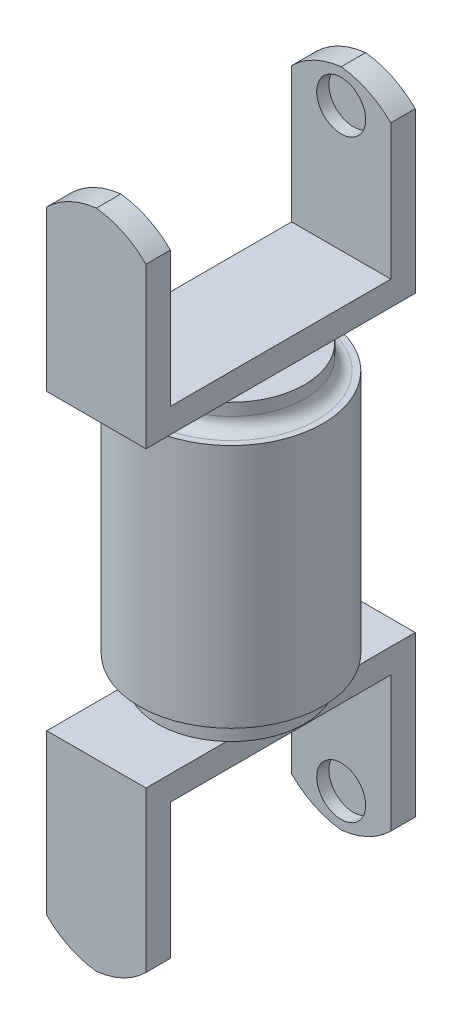
SolidWorks part; units mm, degrees
ref_plane "Front Plane" through (0, 0, 0) normal (0, 0, 1) x (1, 0, 0)
ref_plane "Top Plane" through (0, 0, 0) normal (0, 1, 0) x (1, 0, 0)
ref_plane "Right Plane" through (0, 0, 0) normal (1, 0, 0) x (0, 0, -1)
sketch "Sketch1" plane through (0, 0, 0) normal (0, 1, 0) x (1, 0, 0)
  circle A0 centre (0, 0) radius 7.5
  dimension "D1" = 15
extrude "Boss-Extrude1" add sketch "Sketch1" along normal blind 10
sketch "Sketch5" plane through (0, 10, 0) normal (0, 1, 0) x (1, 0, 0)
  circle A0 centre (0, 0) radius 6
  dimension "D1" = 12
extrude "Boss-Extrude2" add sketch "Sketch5" along normal blind 2
fillet "Fillet2" radius 1 1 edges at (0, 10, 6)
sketch "Sketch6" plane through (0, 0, 0) normal (1, 0, 0) x (0, 0, -1)
  line L0 (6, 12) -> (-6, 12) construction
  line L1 (6, 12) -> (-6, 12)
  line L2 (6, 12) -> (11, 12)
  line L3 (11, 12) -> (11, 27)
  line L4 (11, 27) -> (9, 27)
  line L5 (9, 27) -> (9, 14)
  line L6 (9, 14) -> (-9, 14)
  line L7 (-9, 14) -> (-9, 27)
  line L8 (-9, 27) -> (-11, 27)
  line L9 (-11, 27) -> (-11, 12)
  line L10 (-11, 12) -> (-6, 12)
  dimension "D1" = 15
  dimension "D2" = 2
  dimension "D3" = 13
  dimension "D4" = 5
extrude "Boss-Extrude3" add sketch "Sketch6" along normal blind 6 and the other way blind 6
sketch "Sketch9" plane through (0, 0, 11) normal (0, 0, 1) x (1, 0, 0)
  line L0 (0, 27) -> (0, 12) construction
  line L4 (-6, 12) -> (6, 12)
  line L5 (6, 12) -> (6, 27)
  line L6 (6, 27) -> (-6, 27)
  line L7 (-6, 27) -> (-6, 12)
  line L8 (-6, 12) -> (6, 12)
  line L9 (6, 12) -> (6, 27)
  line L10 (6, 27) -> (-6, 27)
  line L11 (-6, 27) -> (-6, 12)
  arc A0 (0, 27) -> (-6, 19.5) centre (0.75, 20.25) ccw
  arc A1 (0, 27) -> (6, 19.5) centre (-0.75, 20.25) cw
  line M7 (6, 12) -> (6, 27)
  line M8 (6, 27) -> (-6, 27)
  line M9 (-6, 27) -> (-6, 12)
  dimension "D1" = 0
extrude "Cut-Extrude4" cut sketch "Sketch9" against normal blind 29 contours A0 L10 M9 | A1 M8 M7 region at (-4.5286, 25.5286, 11) region at (4.5286, 25.5286, 11)
sketch "Sketch10" plane through (0, 0, 9) normal (0, 0, -1) x (-1, 0, 0)
  line L0 (6, 14) -> (6, 21) construction
  circle A0 centre (0, 24.25) radius 2
  arc A1 (6, 21) -> (0, 27) centre (-0.75, 20.25) ccw construction
  dimension "D1" = 4
  dimension "D2" = 4
  dimension "D3" = 6
extrude "Cut-Extrude5" cut sketch "Sketch10" against normal blind 1 and the other way blind 19
mirror "Mirror2" about plane through (0, 0, 0) normal (0, 1, 0) of "Boss-Extrude1"
mirror "Mirror9" about plane through (0, 0, 0) normal (0, 1, 0) of "Boss-Extrude3", "Boss-Extrude2"
mirror "Mirror11" about plane through (0, 0, 0) normal (0, 1, 0) of "Cut-Extrude5", "Cut-Extrude4"
sketch "Sketch11" plane through (0, 0, -11) normal (0, 0, -1) x (-1, 0, 0)
  line L0 (-4.0523, 25.0523) -> (-4.0523, 12)
  line L1 (4.0523, 25.0523) -> (4.0523, 12)
  line L3 (-6, 21) -> (-6, 12)
  line L4 (-6, 12) -> (6, 12)
  line L5 (6, 12) -> (6, 21)
  line L6 (-6, 21) -> (-6, 12)
  line L7 (-6, 12) -> (6, 12)
  line L8 (6, 12) -> (6, 21)
  arc A2 (0, 27) -> (-6, 21) centre (0.75, 20.25) ccw
  arc A3 (6, 21) -> (0, 27) centre (-0.75, 20.25) ccw
  arc A4 (0, 27) -> (-6, 21) centre (0.75, 20.25) ccw
  arc A5 (6, 21) -> (0, 27) centre (-0.75, 20.25) ccw
  arc M6 (0, 27) -> (-6, 21) centre (0.75, 20.25) ccw
  line M7 (-6, 21) -> (-6, 12)
  line M8 (-6, 12) -> (6, 12)
  line M9 (6, 12) -> (6, 21)
  arc M10 (6, 21) -> (0, 27) centre (-0.75, 20.25) ccw
  dimension "D1" = 0
extrude "Cut-Extrude6" cut sketch "Sketch11" against normal blind 24 contours L0 M6 M7 M8 | L1 M10 M8 M9 region at (4.9766, 17.8566, -11) region at (-4.9766, 17.8566, -11)
mirror "Mirror12" about plane through (0, 0, 0) normal (0, 1, 0) of "Cut-Extrude6"
